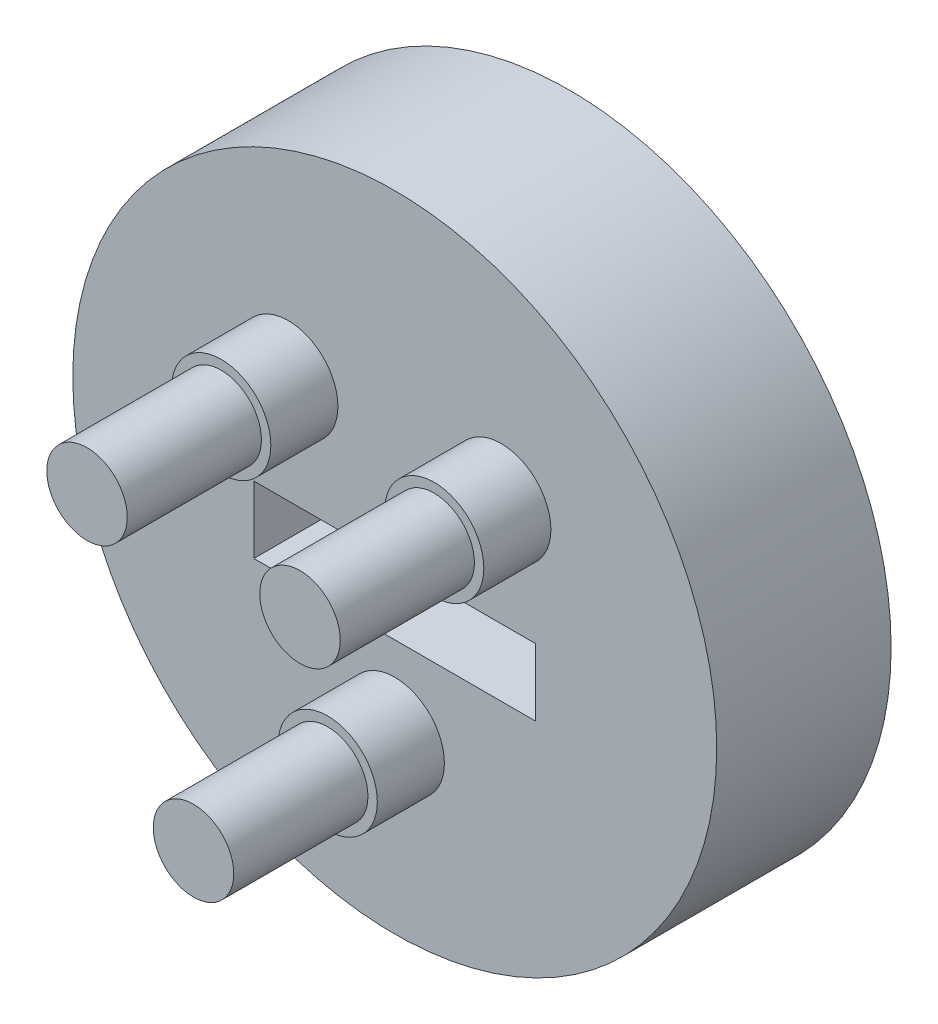
SolidWorks part; units mm, degrees
ref_plane "Front" through (0, 0, 0) normal (0, 0, 1) x (1, 0, 0)
ref_plane "Top" through (0, 0, 0) normal (0, 1, 0) x (1, 0, 0)
ref_plane "Right" through (0, 0, 0) normal (1, 0, 0) x (0, 0, -1)
sketch "Sketch1" plane through (0, 0, 0) normal (0, 0, 1) x (1, 0, 0)
  circle A0 centre (0, 0) radius 24
extrude "Extrude1" add sketch "Sketch1" along normal blind 5
sketch "Sketch2" plane through (0, 0, 5) normal (0, 0, 1) x (1, 0, 0)
  line L0 (-2.5, 0) -> (-10.5, 0)
  line L1 (2.5, 0) -> (10.5, 0)
  line L2 (10.5, 0) -> (10.5, -5)
  line L3 (10.5, -5) -> (-10.5, -5)
  line L4 (-10.5, -5) -> (-10.5, 0)
  circle A0 centre (0, 0) radius 2.5 construction
  arc A1 (2.5, 0) -> (-2.5, 0) centre (0, 0) cw
  circle A2 centre (0, 0) radius 24
extrude "Extrude2" add sketch "Sketch2" along normal blind 8
sketch "Sketch3" plane through (0, 0, 13) normal (0, 0, 1) x (1, 0, 0)
  circle A0 centre (0, 0) radius 2.5
  circle A1 centre (-7.9375, 7.9375) radius 3.7
  circle A2 centre (7.9375, 7.9375) radius 3.7
  circle A3 centre (0, -11.1125) radius 3.7
extrude "Extrude3" add sketch "Sketch3" along normal blind 5
sketch "Sketch5" plane through (0, 0, 18) normal (0, 0, 1) x (1, 0, 0)
  circle A0 centre (-7.9375, 7.9375) radius 3
  circle A1 centre (7.9375, 7.9375) radius 3
  circle A2 centre (0, -11.1125) radius 3
extrude "Extrude6" add sketch "Sketch5" along normal blind 10
sketch "Sketch6" plane through (0, 0, 0) normal (0, 0, -1) x (-1, 0, 0)
  circle A0 centre (0, 12.7) radius 3.175
  circle A1 centre (7.9375, -11.1125) radius 3.175
  circle A2 centre (-7.9375, -11.1125) radius 3.175
extrude "Extrude7" cut sketch "Sketch6" against normal blind 3
